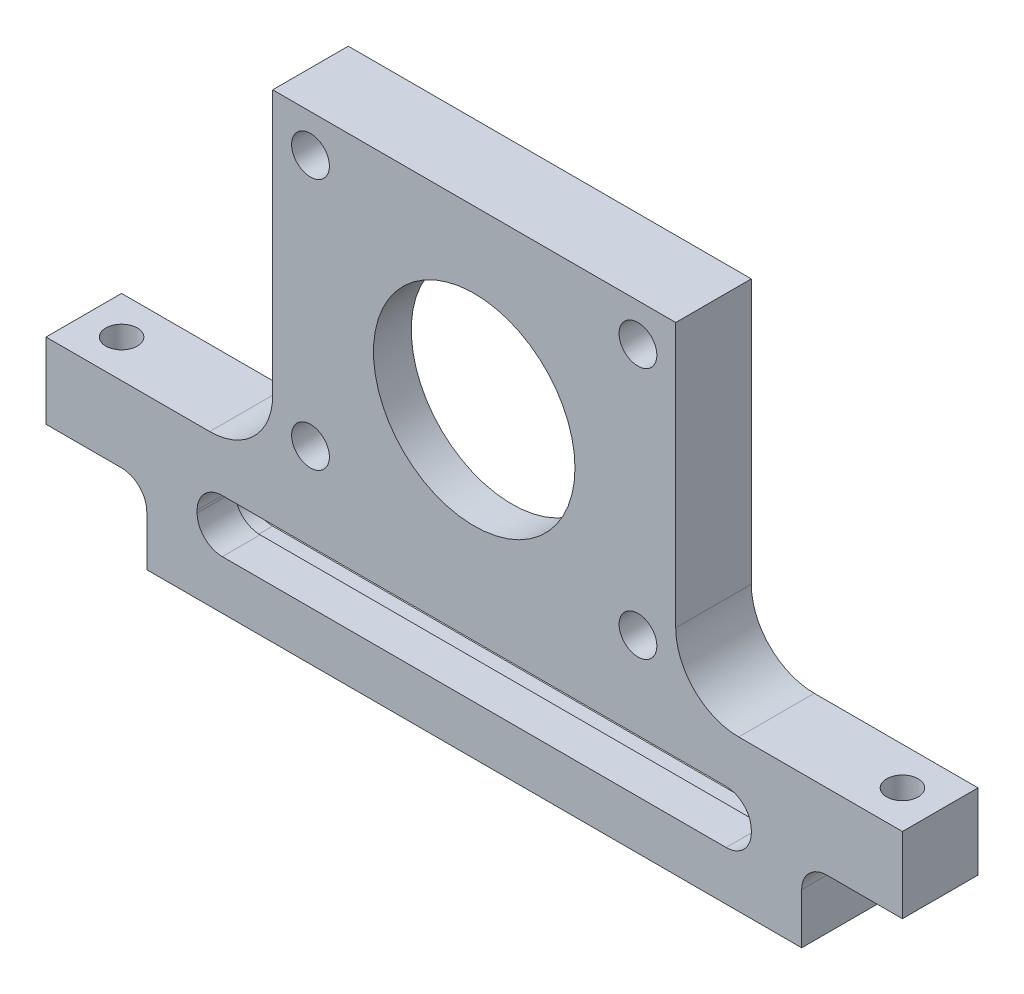
SolidWorks part; units mm, degrees
material "1060 Alloy"
ref_plane "Front Plane" through (0, 0, 0) normal (0, 0, 1) x (1, 0, 0)
ref_plane "Top Plane" through (0, 0, 0) normal (0, 1, 0) x (1, 0, 0)
ref_plane "Right Plane" through (0, 0, 0) normal (1, 0, 0) x (0, 0, -1)
sketch "Sketch1" plane through (0, 0, 0) normal (0, 0, 1) x (1, 0, 0)
  line L0 (0, 0) -> (8, 0)
  line L1 (8, 0) -> (8, -6)
  line L2 (8, -6) -> (60, -6)
  line L3 (60, -6) -> (60, 0)
  line L4 (60, 0) -> (68, 0)
  line L5 (68, 0) -> (68, 6)
  line L6 (68, 6) -> (50, 6)
  line L7 (50, 6) -> (50, 32)
  line L8 (50, 32) -> (18, 32)
  line L9 (18, 32) -> (18, 6)
  line L10 (18, 6) -> (0, 6)
  line L11 (0, 6) -> (0, 0)
  line L13 (12, 2.1) -> (56, 2.1)
  line L14 (12, 2.1) -> (12, -2.1)
  line L15 (12, -2.1) -> (56, -2.1)
  line L16 (56, 2.1) -> (56, -2.1)
  circle A0 centre (34, 18) radius 8
  dimension "D12" = 16
  dimension "D1" = 4.2
  dimension "D2" = 32
  dimension "D3" = 32
  dimension "D4" = 3.9
  dimension "D5" = 6
  dimension "D6" = 3.9
  dimension "D7" = 8
  dimension "D8" = 4
  dimension "D9" = 4
  dimension "D10" = 44
  dimension "D11" = 18
  dimension "D13" = 16
extrude "Boss-Extrude1" add sketch "Sketch1" along normal blind 6
sketch "Sketch3" plane through (0, 0, 0) normal (0, 0, -1) x (-1, 0, 0)
  circle A0 centre (-34, 18) radius 13
  dimension "D1" = 26
extrude "Cut-Extrude2" cut sketch "Sketch3" against normal offset from surface (3 mm away) 3 up to face at (34, 0, 6)
hole_wizard "Tap Drill for M3 Tap1" positions "Sketch5" profile "Sketch4" hole size "M3" standard "ISO"
sketch "Sketch5" plane through (53.9899, 0, -7.4052) normal (0, -1, 0) x (-1, 0, 0)
  line L4 (-14.0101, -13.4052) -> (-14.0101, -7.4052) construction
  line L5 (53.9899, -13.4052) -> (53.9899, -7.4052) construction
  line L7 (-6.0101, -13.4052) -> (-14.0101, -13.4052) construction
  point P0 (50.9899, -10.4052)
  point P2 (-11.0101, -10.4052)
  dimension "D1" = 3
  dimension "D2" = 3
  dimension "D3" = 3
sketch "Sketch4" plane through (3, 0, 3) normal (1, 0, 0) x (0, 0, -1)
  line L0 (0, 0) -> (0, 8.7511)
  line L1 (0, 8.7511) -> (1.25, 8)
  line L2 (1.25, 8) -> (1.25, 0)
  line L5 (1.25, 0) -> (0, 0)
  line L10 (0, 8.7511) -> (-1.25, 8) construction
  line L11 (0, -6.35) -> (0, 107.95) construction
  dimension "Hole Dia." = 2.5
  dimension "Hole Depth" = 8
  dimension "Drill Angle" = 118
sketch "Sketch7" plane through (0, 0, 0) normal (0, 0, -1) x (-1, 0, 0)
  line L1 (-58, 4) -> (-10, 4)
  line L2 (-58, 4) -> (-58, -4)
  line L3 (-58, -4) -> (-10, -4)
  line L4 (-10, 4) -> (-10, -4)
  line L5 (-56, -2.1) -> (-56, 2.1) construction
  line L6 (-56, 2.1) -> (-12, 2.1) construction
  line L9 (-12, 2.1) -> (-12, -2.1) construction
  dimension "D1" = 2
  dimension "D2" = 8
  dimension "D3" = 1.9
  dimension "D4" = 2
extrude "Cut-Extrude4" cut sketch "Sketch7" against normal blind 3
fillet "Fillet1" radius 2 8 edges at (10, -4, 1.5) (12, -2.1, 4.5) (10, 4, 1.5) (12, 2.1, 4.5) (58, -4, 1.5) (56, -2.1, 4.5) (58, 4, 1.5) (56, 2.1, 4.5)
sketch "Sketch8" plane through (0, 0, 6) normal (0, 0, 1) x (1, 0, 0)
  line L0 (18, 32) -> (18, 6) construction
  line L1 (50, 32) -> (18, 32) construction
  line L2 (68, 6) -> (50, 6) construction
  line L3 (50, 6) -> (50, 32) construction
  circle A0 centre (21, 29) radius 1.5
  circle A1 centre (47, 29) radius 1.5
  circle A2 centre (47, 9) radius 1.5
  circle A3 centre (21, 9) radius 1.5
  dimension "D1" = 3
  dimension "D2" = 3
  dimension "D3" = 3
  dimension "D4" = 3
  dimension "D5" = 3
extrude "Cut-Extrude5" cut sketch "Sketch8" against normal up to next
fillet "Fillet2" radius 5 2 edges at (50, 6, 3) (18, 6, 3)
fillet "Fillet3" radius 2 2 edges at (60, 0, 3) (8, 0, 3)
